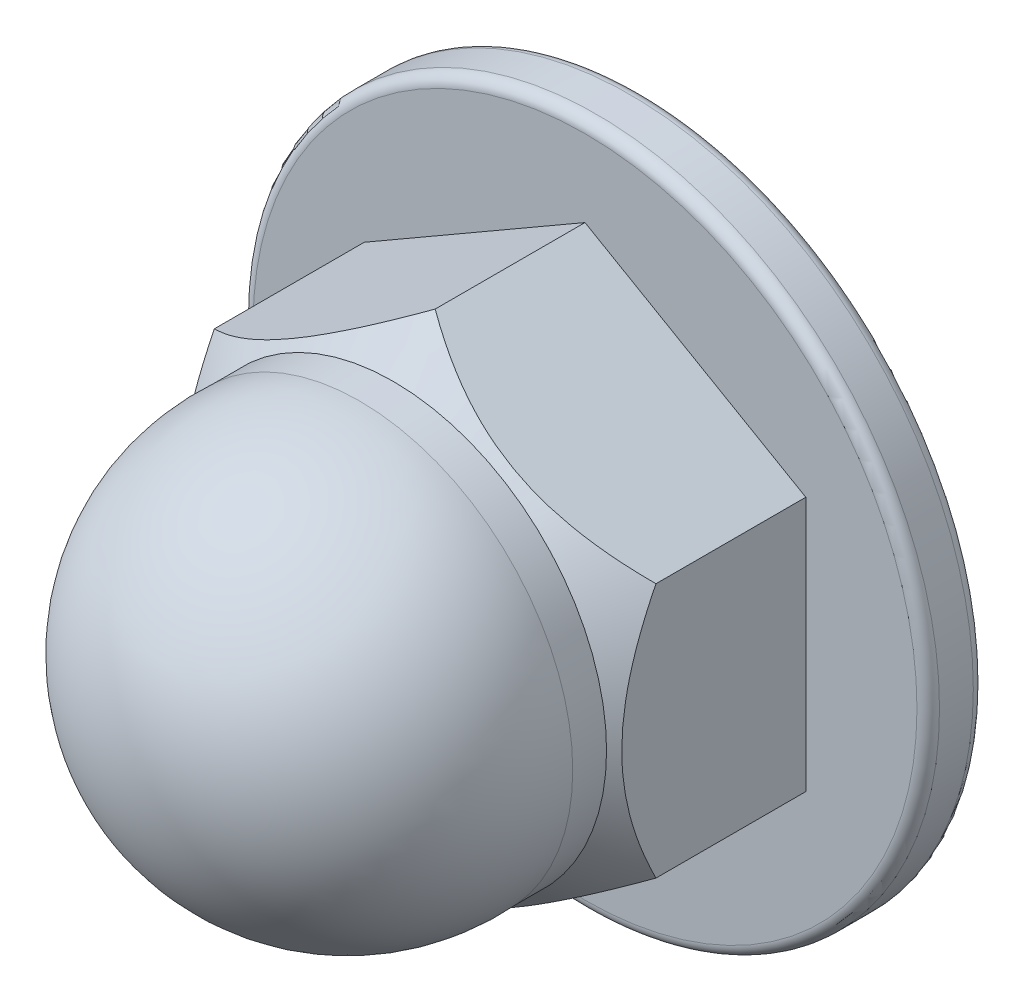
SolidWorks part; units mm, degrees
ref_plane "Front Plane" through (0, 0, 0) normal (0, 0, 1) x (1, 0, 0)
ref_plane "Top Plane" through (0, 0, 0) normal (0, 1, 0) x (1, 0, 0)
ref_plane "Right Plane" through (0, 0, 0) normal (1, 0, 0) x (0, 0, -1)
sketch "Sketch1" plane through (0, 0, 0) normal (0, 0, 1) x (1, 0, 0)
  circle A0 centre (0, 0) radius 30.453
extrude "Boss-Extrude1" add sketch "Sketch1" along normal blind 5
sketch "Sketch2" plane through (0, 0, 5) normal (0, 0, 1) x (1, 0, 0)
  line L1 (0, 22.6186) -> (-19.5883, 11.3093)
  line L2 (-19.5883, 11.3093) -> (-19.5883, -11.3093)
  line L3 (-19.5883, -11.3093) -> (0, -22.6186)
  line L4 (0, -22.6186) -> (19.5883, -11.3093)
  line L5 (19.5883, -11.3093) -> (19.5883, 11.3093)
  line L6 (19.5883, 11.3093) -> (0, 22.6186)
  circle A0 centre (0, 0) radius 19.5883 construction
extrude "Boss-Extrude2" add sketch "Sketch2" along normal blind 17
sketch "Sketch3" plane through (0, 0, 22) normal (0, 0, 1) x (1, 0, 0)
  circle A0 centre (0, 0) radius 18.9129
  circle A2 centre (0, 0) radius 36.4378
extrude "Cut-Extrude1" cut sketch "Sketch3" against normal blind 17 draft 45
sketch "Sketch4" plane through (0, 0, 22) normal (0, 0, 1) x (1, 0, 0)
  circle A0 centre (0, 0) radius 18.9129
extrude "Boss-Extrude3" add sketch "Sketch4" along normal blind 3
dome "Dome1" faces to dome 1 distance 20 reverse direction no elliptical dome no face at (18.9129, 0, 25) parameters "D1"=20
fillet "Fillet1" radius 1 1 edges at (30.453, 0, 5)
fillet "Fillet2" radius 1 1 edges at (30.453, 0, 0)
